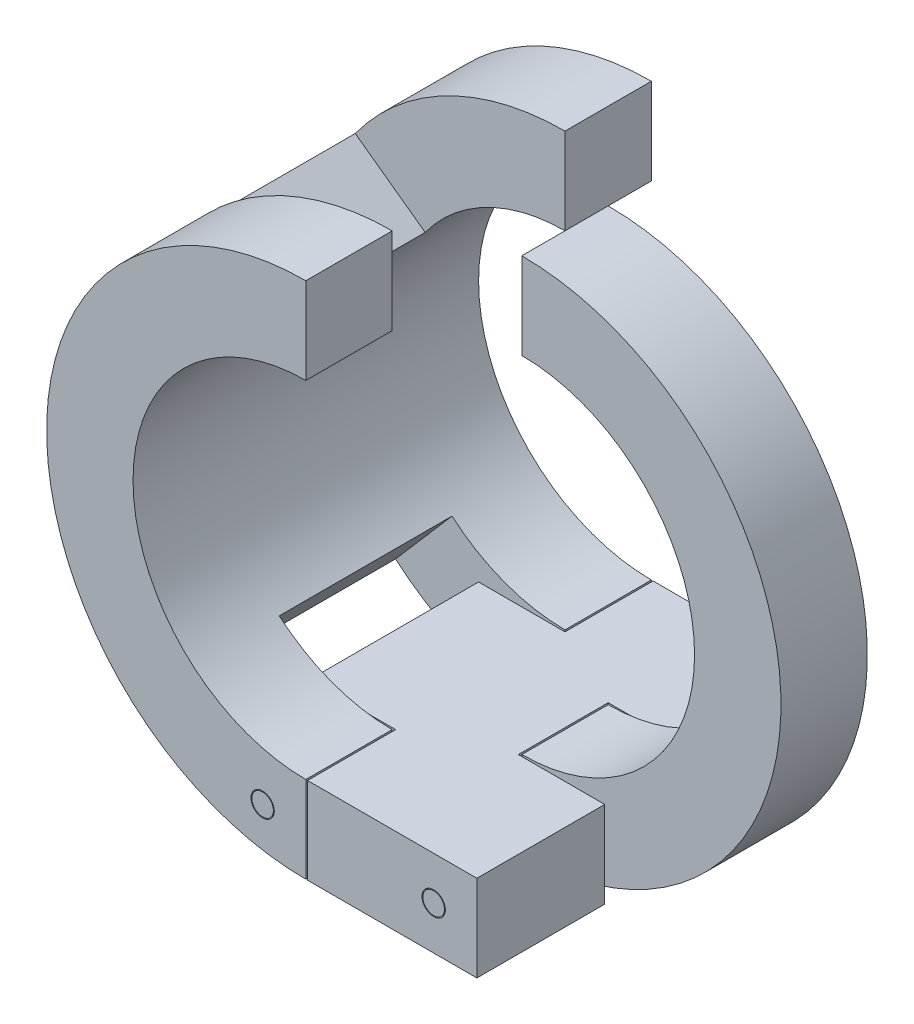
SolidWorks part; units mm, degrees
ref_plane "Front Plane" through (0, 0, 0) normal (0, 0, 1) x (1, 0, 0)
ref_plane "Top Plane" through (0, 0, 0) normal (0, 1, 0) x (1, 0, 0)
ref_plane "Right Plane" through (0, 0, 0) normal (1, 0, 0) x (0, 0, -1)
sketch "Sketch1" plane through (0, 0, 0) normal (0, 0, 1) x (1, 0, 0)
  line L0 (0, 19.05) -> (0, 12.7)
  line L1 (0, -19.05) -> (0, -12.7)
  circle A0 centre (0, 0) radius 6.35
  circle A1 centre (0, 0) radius 19.05
  arc A2 (0, 12.7) -> (0, -12.7) centre (0, 0) ccw
  arc A3 (0, -19.05) -> (0, 19.05) centre (0, 0) cw
  dimension "D1" = 12.7
  dimension "D2" = 38.1
  dimension "D3" = 6.35
  dimension "D4" = 6.35
extrude "Boss-Extrude1" add sketch "Sketch1" along normal blind 6.35 contours A3 L0 A2 L1
ref_plane "Plane1" through (0, 0, 19.05) normal (0, 0, 1) x (1, 0, 0)
sketch "Sketch3" plane through (0, 0, 19.05) normal (0, 0, 1) x (1, 0, 0)
  line L0 (0, -19.05) -> (0, -12.7) construction
  line L1 (0, 19.05) -> (0, 12.7) construction
  line L2 (0, -19.05) -> (0, -12.7)
  line L3 (0, 19.05) -> (0, 12.7)
  arc A0 (0, 12.7) -> (0, -12.7) centre (0, 0) ccw construction
  arc A1 (0, 19.05) -> (0, -19.05) centre (0, 0) ccw construction
  arc A2 (0, 12.7) -> (0, -12.7) centre (0, 0) ccw
  arc A3 (0, 19.05) -> (0, -19.05) centre (0, 0) ccw
extrude "Boss-Extrude2" add sketch "Sketch3" along normal blind 6.35 separate body contours L2 A2 L3 A3
ref_plane "Plane2" through (0, 0, 12.7) normal (0, 0, 1) x (1, 0, 0)
sketch "Sketch4" plane through (0, 0, 12.7) normal (0, 0, 1) x (1, 0, 0)
  line L0 (6.35, 19.05) -> (6.35, 12.7)
  line L1 (0, 19.05) -> (0, 12.7) construction
  line L2 (6.35, -12.7) -> (6.35, -19.05)
  arc A0 (6.35, -12.7) -> (6.35, 12.7) centre (6.35, 0) ccw
  arc A1 (6.35, 19.05) -> (6.35, -19.05) centre (6.35, 0) cw
  dimension "D1" = 6.35
  dimension "D2" = 6.35
  dimension "D3" = 6.35
extrude "Boss-Extrude3" add sketch "Sketch4" along normal blind 3.175 and the other way blind 3.175 separate body contours A1 L2 A0 L0
sketch "Sketch5" plane through (0, 0, 6.35) normal (0, 0, 1) x (1, 0, 0)
  line L0 (-10.2768, 7.4618) -> (-15.4151, 11.1927)
  line L1 (-8.3032, -9.6097) -> (-12.4548, -14.4146)
  arc A0 (0, 12.7) -> (0, -12.7) centre (0, 0) ccw construction
  arc A1 (0, 19.05) -> (0, -19.05) centre (0, 0) ccw construction
  arc A2 (-10.2768, 7.4618) -> (-8.3032, -9.6097) centre (0, 0) ccw
  arc A3 (-15.4151, 11.1927) -> (-12.4548, -14.4146) centre (0, 0) ccw
extrude "Boss-Extrude4" add sketch "Sketch5" along normal up to surface (12.7 mm away) contours A3 L1 A2 L0 up to face at (-7.9375, 0, 19.05)
ref_plane "Plane3" through (0, -19.05, 0) normal (0, 1, 0) x (0, 0, -1)
sketch "Sketch6" plane through (0, -19.05, 0) normal (0, 1, 0) x (0, 0, -1)
  line L0 (-25.4, -0.127) -> (-18.923, -0.127)
  line L3 (-18.923, -0.127) -> (-18.923, 6.223)
  line L4 (-18.923, 6.223) -> (-6.477, 6.223)
  line L5 (-6.477, 6.223) -> (-6.477, -0.127)
  line L6 (-6.477, -0.127) -> (0, -0.127)
  line L7 (0, -0.127) -> (0, -12.573)
  line L8 (0, -12.573) -> (-9.398, -12.573)
  line L9 (-9.525, -6.35) -> (-15.875, -6.35) construction
  line L10 (-9.398, -12.573) -> (-9.398, -6.223)
  line L11 (-9.398, -6.223) -> (-16.002, -6.223)
  line L12 (-16.002, -6.223) -> (-16.002, -12.573)
  line L13 (-9.525, -6.35) -> (-15.875, -6.35)
  line L14 (-16.002, -12.573) -> (-25.4, -12.573)
  line L15 (-25.4, -12.573) -> (-25.4, -0.127)
  line L16 (-25.4, 0) -> (-19.05, 0) construction
  line L17 (-6.35, 0) -> (0, 0) construction
  line L18 (-6.35, 12.4548) -> (-6.35, 0) construction
  line L19 (-19.05, 5.1922) -> (-19.05, -5.1922) construction
  dimension "D1" = 6.35
  dimension "D2" = 0.127
  dimension "D3" = 9.398
  dimension "D4" = 9.398
  dimension "D5" = 0.127
  dimension "D6" = 0.127
  dimension "D7" = 0.127
  dimension "D8" = 0.127
  dimension "D9" = 6.35
  dimension "D10" = 25.4
  dimension "D11" = 2.921
extrude "Boss-Extrude5" add sketch "Sketch6" along normal blind 6.35 separate body contours L15 L14 L12 L11 L10 L8 L7 L6 L5 L4 L3 L0 region at (3.8854, -19.05, 12.7)
sketch "Sketch7" plane through (0, 0, 25.4) normal (0, 0, 1) x (1, 0, 0)
  line L0 (12.573, -12.7) -> (12.573, -19.05) construction
  line L1 (12.573, -12.7) -> (0.127, -12.7) construction
  line L2 (6.223, -12.7) -> (6.223, -19.05) construction
  line L3 (12.573, -19.05) -> (0.127, -19.05) construction
  line L5 (0, -19.05) -> (0, -12.7) construction
  circle A0 centre (9.398, -15.875) radius 0.8572
  circle A1 centre (-3.175, -15.875) radius 0.8572
  dimension "D5" = 1.7145
  dimension "D2" = 3.175
  dimension "D3" = 3.175
  dimension "D4" = 6.35
  dimension "D6" = 3.175
  dimension "D7" = 3.175
extrude "Cut-Extrude1" cut sketch "Sketch7" against normal through all both and the other way through all contours A0 | A1 region at (9.398, -15.875, 25.4)
sketch "Sketch8" plane through (0, 0, 25.4) normal (0, 0, 1) x (1, 0, 0)
  circle A0 centre (-3.175, -15.875) radius 0.7938
  circle A1 centre (9.398, -15.875) radius 0.7937
  dimension "D1" = 1.5875
  dimension "D2" = 1.5875
extrude "Boss-Extrude6" add sketch "Sketch8" against normal through all contours A0 | A1
